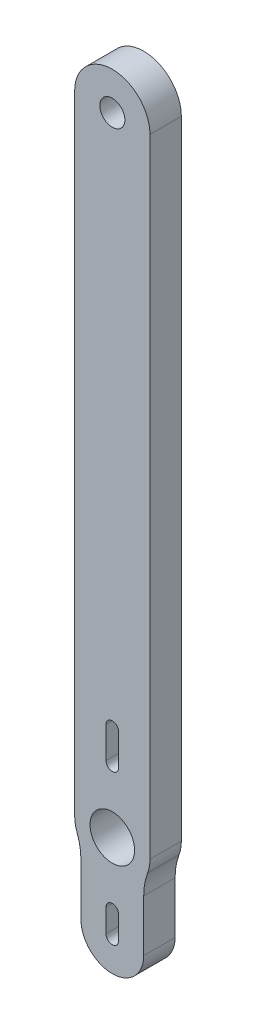
SolidWorks part; units mm, degrees
ref_plane "Front Plane" through (0, 0, 0) normal (0, 0, 1) x (1, 0, 0)
ref_plane "Top Plane" through (0, 0, 0) normal (0, 1, 0) x (1, 0, 0)
ref_plane "Right Plane" through (0, 0, 0) normal (1, 0, 0) x (0, 0, -1)
sketch "Model" plane through (0, 0, 0) normal (0, 0, 1) x (1, 0, 0)
  line L0 (-1, 18.4215) -> (-1, -3.4062) construction
  line L1 (1, 18.4215) -> (1, 5.9161) construction
  line L2 (-6, 0) -> (-6, 100)
  line L3 (6, 0) -> (6, 100)
  line L7 (-7.5978, 10.1) -> (4.5933, 10.1) construction
  line L8 (-1.9126, -10.1) -> (1, -10.1) construction
  line L9 (-3.5953, 15.1) -> (3.0222, 15.1) construction
  line L10 (-2.3019, -13.8) -> (3.0222, -13.8) construction
  line L13 (-1, -10.1) -> (-1, -13.8)
  line L14 (1, -10.1) -> (1, -13.8)
  line L15 (-1, 15.1) -> (-1, 10.1)
  line L16 (1, 15.1) -> (1, 10.1)
  line L17 (1, 3.4062) -> (1, -5.9161) construction
  line L18 (1, -10.1) -> (1, -18.7667) construction
  line L19 (-1, -5.9161) -> (-1, -18.7667) construction
  line L20 (-5, -5.5678) -> (-5, -13.8)
  line L21 (5, -5.5678) -> (5, -13.8)
  circle A0 centre (0, 0) radius 3.55
  arc A1 (-6, 0) -> (-5.625, -2.0879) centre (0, 0) ccw
  arc A2 (1, 15.1) -> (-1, 15.1) centre (0, 15.1) ccw
  arc A3 (-1, 10.1) -> (1, 10.1) centre (0, 10.1) ccw
  arc A4 (1, -10.1) -> (-1, -10.1) centre (0, -10.1) ccw
  arc A5 (-1, -13.8) -> (1, -13.8) centre (0, -13.8) ccw
  arc A6 (6, 100) -> (-6, 100) centre (0, 100) ccw
  circle A7 centre (0, 100) radius 2
  arc A8 (-5, -13.8) -> (5, -13.8) centre (0, -13.8) ccw
  arc A9 (5.625, -2.0879) -> (6, 0) centre (0, 0) ccw
  arc A11 (5.625, -2.0879) -> (5, -5.5678) centre (15, -5.5678) ccw
  arc A12 (-5.625, -2.0879) -> (-5, -5.5678) centre (-15, -5.5678) cw
  point P44 (5, -3.3166)
  point P47 (-5, -3.3166)
  dimension "D1" = 7.1
  dimension "D2" = 12
  dimension "D5" = 4
  dimension "D6" = 100
  dimension "D3" = 1
  dimension "D4" = 1
  dimension "D9" = 10.1
  dimension "D10" = 10.1
  dimension "D11" = 3.7
  dimension "D12" = 5
extrude "Boss-Extrude1" add sketch "Model" along normal blind 5
